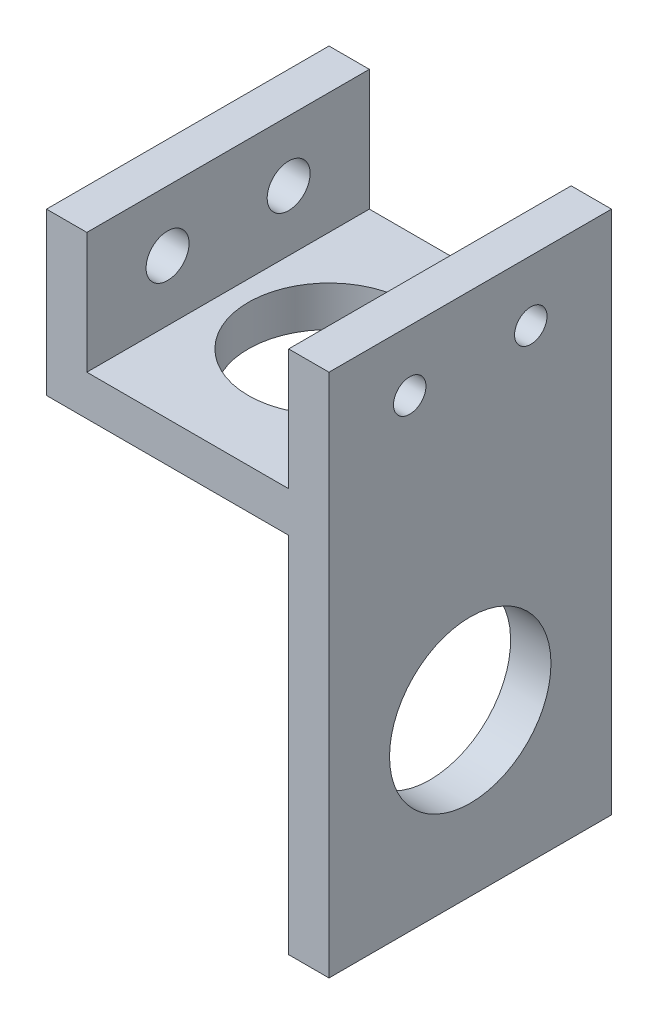
SolidWorks part; units mm, degrees
ref_plane "Front" through (0, 0, 0) normal (0, 0, 1) x (1, 0, 0)
ref_plane "Top" through (0, 0, 0) normal (0, 1, 0) x (1, 0, 0)
ref_plane "Right" through (0, 0, 0) normal (1, 0, 0) x (0, 0, -1)
sketch "Sketch1" plane through (0, 0, 0) normal (0, 0, 1) x (1, 0, 0)
  line L0 (0, 0) -> (6.35, 0)
  line L1 (6.35, 0) -> (6.35, 82.55)
  line L2 (6.35, 82.55) -> (0, 82.55)
  line L3 (0, 82.55) -> (0, 63.5)
  line L4 (0, 63.5) -> (-31.75, 63.5)
  line L5 (-31.75, 63.5) -> (-31.75, 82.55)
  line L6 (-31.75, 82.55) -> (-38.1, 82.55)
  line L7 (-38.1, 82.55) -> (-38.1, 57.15)
  line L8 (-38.1, 57.15) -> (0, 57.15)
  line L9 (0, 57.15) -> (0, 0)
  point P3 (3.175, 0)
  point P12 (-25.5294, 57.15)
  dimension "D1" = 6.35
  dimension "D2" = 57.15
  dimension "D3" = 31.75
  dimension "D4" = 6.35
  dimension "D5" = 6.35
  dimension "D6" = 19.05
  dimension "D7" = 19.05
  dimension "D8" = 6.35
extrude "Boss-Extrude1" add sketch "Sketch1" along normal blind 44.45
sketch "Sketch2" plane through (0, 0, 0) normal (-1, 0, 0) x (0, 0, 1)
  line L0 (44.45, 0) -> (0, 0) construction
  line L1 (44.45, 57.15) -> (44.45, 0) construction
  circle A0 centre (22.225, 25.4) radius 12.7
  point P4 (0, 0)
  dimension "D3" = 25.4
  dimension "D1" = 25.4
  dimension "D2" = 22.225
extrude "Cut-Extrude1" cut sketch "Sketch2" against normal blind 44.45
hole_wizard "1/4-20 Tapped Hole1" positions "Sketch3" profile "Sketch4" tap size "1/4-20" standard "ANSI Inch" end condition through all
sketch "Sketch3" plane through (0, 0, 0) normal (-1, 0, 0) x (0, 0, 1)
  line L2 (44.45, 82.55) -> (0, 82.55) construction
  line L3 (0, 82.55) -> (0, 63.5) construction
  point P0 (12.7, 73.025)
  point P2 (31.75, 73.025)
  point P23 (0, 0)
  dimension "D1" = 19.05
  dimension "D2" = 9.525
  dimension "D3" = 12.7
sketch "Sketch4" plane through (0, 73.025, 12.7) normal (0, 1, 0) x (0, 0, 1)
  line L0 (0, 0) -> (0, 6.35)
  line L1 (0, 6.35) -> (2.5527, 6.35)
  line L2 (2.5527, 6.35) -> (2.5527, 0)
  line L5 (2.5527, 0) -> (0, 0)
  line L11 (0, -6.35) -> (0, 107.95) construction
  dimension "Thru Tap Drill Dia." = 5.1054
  dimension "Thru Tap Drill Depth" = 6.35
cosmetic thread "Hole Thread1" parameters "D2"=6.35
cosmetic thread "Hole Thread2" parameters "D2"=6.35
sketch "Sketch5" plane through (-38.1, 0, 0) normal (-1, 0, 0) x (0, 0, 1)
  line L0 (44.45, 82.55) -> (0, 82.55) construction
  line L1 (44.45, 82.55) -> (44.45, 57.15) construction
  circle A0 centre (12.7, 73.025) radius 3.3782
  circle A1 centre (31.75, 73.025) radius 3.3782
  point P8 (0, 0)
  point P9 (0, 0)
  dimension "D4" = 6.7564
  dimension "D1" = 19.05
  dimension "D2" = 9.525
  dimension "D3" = 12.7
extrude "Cut-Extrude2" cut sketch "Sketch5" against normal blind 8.89
sketch "Sketch6" plane through (0, 63.5, 0) normal (0, 1, 0) x (1, 0, 0)
  line L0 (6.35, -44.45) -> (0, -44.45) construction
  line L2 (0, -44.45) -> (0, 0) construction
  circle A0 centre (-15.875, -22.225) radius 12.7
  dimension "D1" = 25.4
  dimension "D2" = 22.225
  dimension "D3" = 15.875
extrude "Cut-Extrude3" cut sketch "Sketch6" against normal blind 8.89
